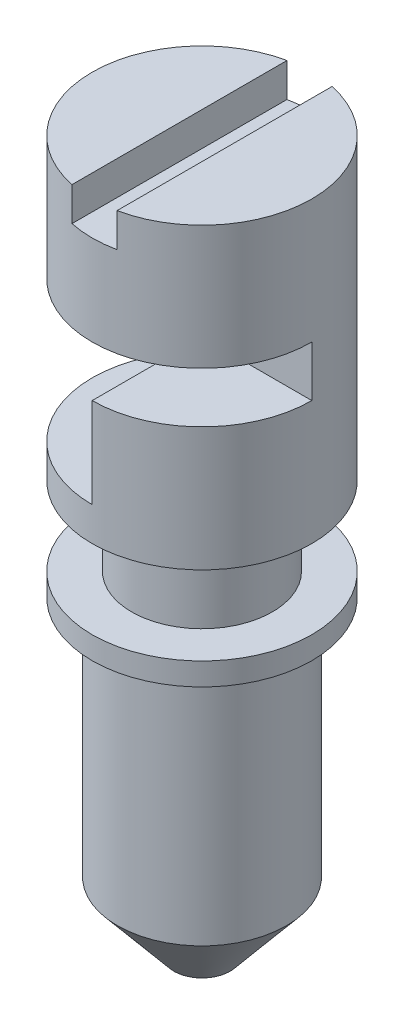
SolidWorks part; units mm, degrees
material "Chrome Stainless Steel"
ref_plane "Front Plane" through (0, 0, 0) normal (0, 0, 1) x (1, 0, 0)
ref_plane "Top Plane" through (0, 0, 0) normal (0, 1, 0) x (1, 0, 0)
ref_plane "Right Plane" through (0, 0, 0) normal (1, 0, 0) x (0, 0, -1)
ref_axis "CentralAxis" through (0, 5.6881, 0) along (0, -1, 0)
sketch "BaseS" plane through (0, 0, 0) normal (0, 1, 0) x (1, 0, 0)
  circle A0 centre (0, 0) radius 1.95
  dimension "Dia" = 3.9
extrude "Base" add sketch "BaseS" along normal blind 5.3
sketch "ScrewSlotS" plane through (0, 5.3, 0) normal (0, 1, 0) x (1, 0, 0)
  line L1 (-0.4, 1.95) -> (0.4, 1.95)
  line L2 (-0.4, 1.95) -> (-0.4, -1.95)
  line L3 (-0.4, -1.95) -> (0.4, -1.95)
  line L4 (0.4, 1.95) -> (0.4, -1.95)
  line L5 (-0.4, 1.95) -> (0.4, -1.95) construction
  line L6 (-0.4, -1.95) -> (0.4, 1.95) construction
  circle A0 centre (0, 0) radius 1.95 construction
  point P0 (0, 0)
  dimension "Width" = 0.8
extrude "ScrewSlot" cut sketch "ScrewSlotS" against normal blind 0.6
sketch "MainSlotS" plane through (0, 0, 0) normal (0, 0, 1) x (1, 0, 0)
  line L0 (-1.95, 5.3) -> (-1.95, 0) construction
  line L1 (0, 0.6) -> (-1.95, 0.6)
  line L2 (0, 0.6) -> (0, 3.1)
  line L3 (0, 3.1) -> (-1.95, 3.1)
  line L4 (-1.95, 0.6) -> (-1.95, 3.1)
  line L5 (0, 0.6) -> (-1.95, 3.1) construction
  line L6 (0, 3.1) -> (-1.95, 0.6) construction
  line L9 (1.95, 5.3) -> (-1.95, 5.3) construction
  point P0 (-0.975, 1.85)
  dimension "D1" = 2.2
  dimension "Height" = 2.5
extrude "MainSlot" cut sketch "MainSlotS" against normal through all both and the other way through all
sketch "SmallSlotS" plane through (0, 0, 0) normal (1, 0, 0) x (0, 0, -1)
  line L1 (0, 2.2) -> (-1.95, 2.2)
  line L2 (0, 2.2) -> (0, 3.1)
  line L3 (0, 3.1) -> (-1.95, 3.1)
  line L4 (-1.95, 2.2) -> (-1.95, 3.1)
  line L5 (0, 2.2) -> (-1.95, 3.1) construction
  line L6 (0, 3.1) -> (-1.95, 2.2) construction
  line L8 (1.95, 3.1) -> (-1.95, 3.1) construction
  line L9 (-1.95, 0.6) -> (-1.95, 3.1) construction
  point P0 (-0.975, 2.65)
  dimension "Height" = 0.9
extrude "SmallSlot" cut sketch "SmallSlotS" against normal through all both and the other way through all
sketch "O-RingBodyS" plane through (0, 0, 0) normal (0, 0, 1) x (1, 0, 0)
  line L1 (-1.25, 0) -> (0, 0)
  line L2 (-1.25, 0) -> (-1.25, -1.4)
  line L5 (-1.25, -1.4) -> (-1.95, -1.4)
  line L6 (0, 0) -> (0, -7.3) construction
  line L8 (-1.95, -1.4) -> (-1.95, -1.8)
  line L9 (-1.95, -1.8) -> (-1.5, -1.8)
  line L10 (-1.5, -1.8) -> (-1.5, -6.1)
  line L11 (-1.5, -6.1) -> (-0.5, -7.3)
  line L12 (-0.5, -7.3) -> (0, -7.3)
  line L13 (-1.95, 0.6) -> (-1.95, 0) construction
  line L15 (0, 0) -> (0, -7.3)
  point P1 (0, 0)
  point P3 (0, 0)
  dimension "D1" = 0.4
  dimension "Width" = 1.4
  dimension "D2" = 0.7
  dimension "D3" = 2.5
  dimension "D4" = 5.5
  dimension "D5" = 3
  dimension "D6" = 1
  dimension "D7" = 1.2
revolve "O-RingBody" add sketch "O-RingBodyS" angle 360 about L6
